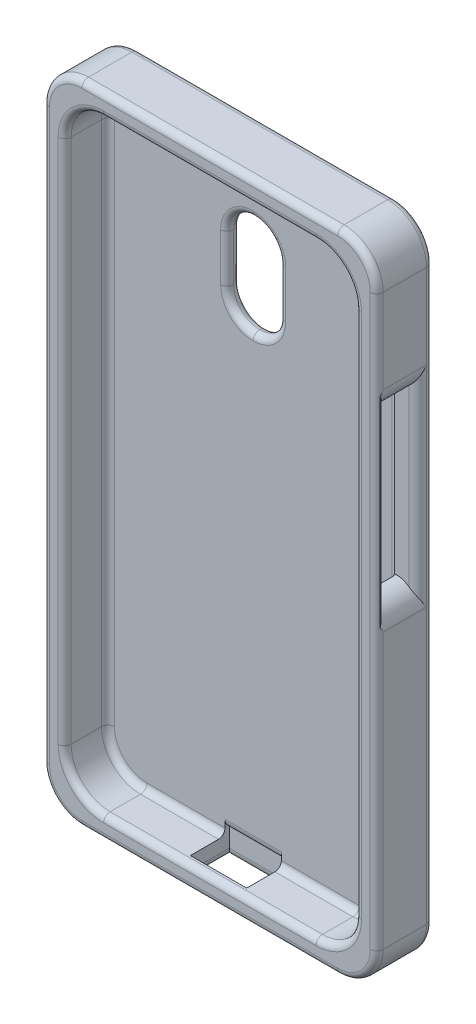
SolidWorks part; units mm, degrees
ref_plane "Front" through (0, 0, 0) normal (0, 0, 1) x (1, 0, 0)
ref_plane "Top" through (0, 0, 0) normal (0, 1, 0) x (1, 0, 0)
ref_plane "Right" through (0, 0, 0) normal (1, 0, 0) x (0, 0, -1)
sketch "Sketch1" plane through (0, 0, 0) normal (0, 0, 1) x (1, 0, 0)
  line L0 (0, 0) -> (0, 45.43) construction
  line L1 (38.5, 74.65) -> (-38.5, 74.65)
  line L2 (38.5, 74.65) -> (38.5, -74.65)
  line L3 (38.5, -74.65) -> (-38.5, -74.65)
  line L4 (-38.5, 74.65) -> (-38.5, -74.65)
  line L5 (38.5, 74.65) -> (-38.5, -74.65) construction
  line L6 (38.5, -74.65) -> (-38.5, 74.65) construction
  line L11 (38.5, -74.65) -> (-38.5, 74.65) construction
  line L12 (38.5, 74.65) -> (-38.5, -74.65) construction
  line L14 (-6, 56.93) -> (6, 56.93)
  line L15 (-6, 56.93) -> (-6, 33.93)
  line L16 (-6, 33.93) -> (6, 33.93)
  line L17 (6, 56.93) -> (6, 33.93)
  line L18 (-6, 56.93) -> (6, 33.93) construction
  line L19 (-6, 33.93) -> (6, 56.93) construction
  point P0 (0, 0)
  point P6 (0, 0)
  dimension "D1" = 149.3
  dimension "D2" = 77
  dimension "D3" = 29.22
  dimension "D4" = 12
  dimension "D5" = 23
extrude "Boss-Extrude1" add sketch "Sketch1" along normal blind 3
sketch "Sketch2" plane through (0, 0, 3) normal (0, 0, 1) x (1, 0, 0)
  line L0 (38.5, 74.65) -> (-38.5, 74.65) construction
  line L1 (38.5, -74.65) -> (-38.5, -74.65)
  line L2 (38.5, -74.65) -> (38.5, 74.65)
  line L3 (38.5, 74.65) -> (-38.5, 74.65)
  line L4 (-38.5, -74.65) -> (-38.5, 74.65)
  line L5 (38.5, -74.65) -> (-38.5, 74.65) construction
  line L6 (38.5, 74.65) -> (-38.5, -74.65) construction
  line L7 (-38.5, 74.65) -> (-38.5, -74.65) construction
  line L13 (37.4685, -72.65) -> (-37.4685, 72.65) construction
  line L14 (37.4685, 72.65) -> (-37.4685, -72.65) construction
  line L15 (33.5, -69.65) -> (-33.5, -69.65)
  line L16 (33.5, -69.65) -> (33.5, 69.65)
  line L17 (33.5, 69.65) -> (-33.5, 69.65)
  line L18 (-33.5, -69.65) -> (-33.5, 69.65)
  line L19 (33.5, -69.65) -> (-33.5, 69.65) construction
  line L20 (33.5, 69.65) -> (-33.5, -69.65) construction
  point P0 (0, 0)
  point P10 (0, 0)
  point P15 (0, 0)
  dimension "D1" = 5
  dimension "D2" = 5
extrude "Boss-Extrude2" add sketch "Sketch2" along normal blind 10
fillet "Fillet1" radius 9 1 edges at (-33.5, 69.65, 8)
fillet "Fillet2" radius 9 1 edges at (33.5, 69.65, 8)
fillet "Fillet3" radius 9 1 edges at (-33.5, -69.65, 8)
fillet "Fillet4" radius 9 1 edges at (33.5, -69.65, 8)
fillet "Fillet5" radius 9 1 edges at (-38.5, 74.65, 6.5)
fillet "Fillet6" radius 9 1 edges at (38.5, 74.65, 6.5)
fillet "Fillet7" radius 9 2 edges at (38.5, -74.65, 6.5) (-38.5, -74.65, 6.5)
fillet "Fillet9" radius 6 4 edges at (6, 56.93, 1.5) (6, 33.93, 1.5) (-6, 33.93, 1.5) (-6, 56.93, 1.5)
fillet "Fillet10" radius 1.5 14 edges at (6, 45.43, 3) (4.2426, 55.1726, 3) (-4.2426, 55.1726, 3) (-6, 45.43, 3) (-4.2426, 35.6874, 3) (4.2426, 35.6874, 3) (-30.864, -67.014, 3) (-33.5, 0, 3) (-30.864, 67.014, 3) (0, 69.65, 3) (30.864, 67.014, 3) (33.5, 0, 3) (30.864, -67.014, 3) (0, -69.65, 3)
fillet "Fillet11" radius 1.5 14 edges at (-4.2426, 55.1726, 0) (4.2426, 55.1726, 0) (6, 45.43, 0) (4.2426, 35.6874, 0) (-4.2426, 35.6874, 0) (-6, 45.43, 0) (35.864, 72.014, 0) (0, 74.65, 0) (-35.864, 72.014, 0) (-38.5, 0, 0) (-35.864, -72.014, 0) (0, -74.65, 0) (35.864, -72.014, 0) (38.5, 0, 0)
sketch "Sketch4" plane through (0, 0, 0) normal (0, 1, 0) x (1, 0, 0)
  line L0 (0, 0) -> (0, 0.85) construction
  line L1 (-29.5, 0) -> (29.5, 0) construction
  line L3 (1.5, 1.7) -> (1.5, 0)
  line L4 (1.5, 0) -> (-1.5, 0)
  line L5 (-1.5, 1.7) -> (-1.5, 0)
  line L6 (1.5, 1.7) -> (-1.5, 0) construction
  line L7 (1.5, 0) -> (-1.5, 1.7) construction
  line L8 (0, 0.85) -> (0, 3.2) construction
  line L9 (-1.5, 1.7) -> (-2.65, 1.7)
  line L10 (2.65, 4.7) -> (-2.65, 4.7)
  line L11 (2.65, 4.7) -> (2.65, 1.7)
  line L12 (2.65, 1.7) -> (1.5, 1.7)
  line L13 (-2.65, 4.7) -> (-2.65, 1.7)
  line L14 (2.65, 4.7) -> (-2.65, 1.7) construction
  line L15 (2.65, 1.7) -> (-2.65, 4.7) construction
  dimension "D1" = 3
  dimension "D2" = 4.7
  dimension "D3" = 5.3
  dimension "D4" = 3
extrude "Boss-Extrude3" add sketch "Sketch4" along normal blind 1 and the other way blind 73 contours L10 L13 L9 L5 L4 L3 L12 L11
sketch "Sketch5" plane through (0, 0, 0) normal (1, 0, 0) x (0, 0, -1)
  line L0 (-7.1389, 74.65) -> (-7.1389, 41.15) construction
  line L1 (-13, 74.65) -> (-1.5, 74.65) construction
  line L2 (-7.1389, 41.15) -> (-7.1389, 2.75) construction
  line L4 (-3.5056, 2.75) -> (-10.7722, 2.75)
  line L5 (-3.5056, 2.75) -> (-3.5056, 41.15)
  line L6 (-3.5056, 41.15) -> (-10.7722, 41.15)
  line L7 (-10.7722, 2.75) -> (-10.7722, 41.15)
  line L8 (-3.5056, 2.75) -> (-10.7722, 41.15) construction
  line L9 (-3.5056, 41.15) -> (-10.7722, 2.75) construction
  point P2 (-7.1389, 21.95)
  dimension "D1" = 33.5
  dimension "D2" = 38.4
extrude "Cut-Extrude1" cut sketch "Sketch5" along normal blind 46 contours L7 L6 L5 L4
fillet "Fillet13" radius 1.5 16 edges at (30.864, -67.014, 13) (33.5, 0, 13) (30.864, 67.014, 13) (0, 69.65, 13) (-30.864, 67.014, 13) (-33.5, 0, 13) (-30.864, -67.014, 13) (0, -69.65, 13) (-35.864, -72.014, 13) (-38.5, 0, 13) (-35.864, 72.014, 13) (0, 74.65, 13) (35.864, 72.014, 13) (38.5, 0, 13) (35.864, -72.014, 13) (0, -74.65, 13)
fillet "Fillet15" radius 5 2 edges at (38.5, 2.75, 7.1389) (38.5, 41.15, 7.1389)
fillet "Fillet16" radius 2 2 edges at (38.5, 21.95, 10.7722) (38.5, 21.95, 3.5056)
sketch "Sketch7" plane through (0, -74.65, 0) normal (0, -1, 0) x (-1, 0, 0)
  line L0 (29.5, -6.5) -> (-29.5, -6.5) construction
  line L1 (29.5, -11.5) -> (29.5, -1.5) construction
  line L2 (-29.5, -1.5) -> (-29.5, -11.5) construction
  line L4 (-6.5, -2) -> (6.5, -2)
  line L5 (-6.5, -2) -> (-6.5, -11)
  line L6 (-6.5, -11) -> (6.5, -11)
  line L7 (6.5, -2) -> (6.5, -11)
  line L8 (-6.5, -2) -> (6.5, -11) construction
  line L9 (-6.5, -11) -> (6.5, -2) construction
  point P6 (0, -6.5)
  dimension "D1" = 13
  dimension "D2" = 9
extrude "Cut-Extrude3" cut sketch "Sketch7" against normal blind 6.5
fillet "Fillet17" radius 2 2 edges at (-6.5, -74.65, 6.5) (6.5, -74.65, 6.5)
fillet "Fillet18" radius 2 2 edges at (0, -74.65, 11) (0, -74.65, 2)
fillet "Fillet19" radius 2 1 edges at (0, -68.15, 3)
